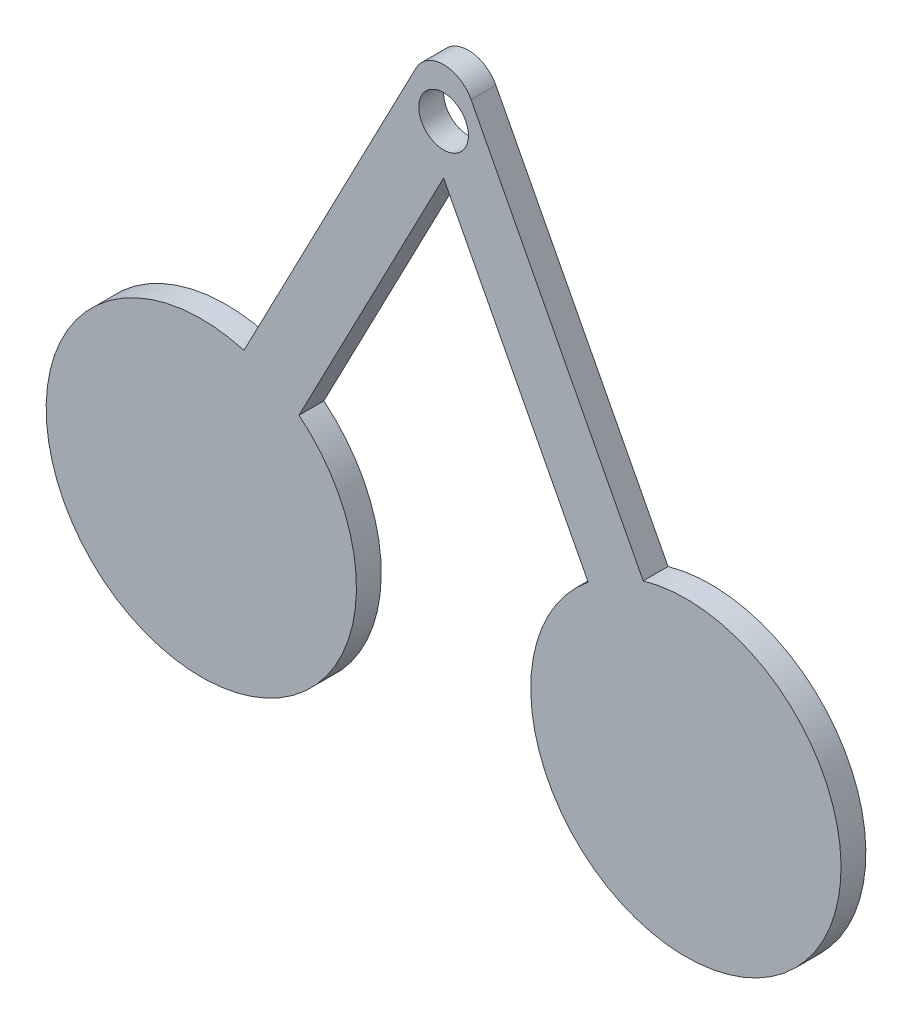
SolidWorks part; units mm, degrees
ref_plane "Front Plane" through (0, 0, 0) normal (0, 0, 1) x (1, 0, 0)
ref_plane "Top Plane" through (0, 0, 0) normal (0, 1, 0) x (1, 0, 0)
ref_plane "Right Plane" through (0, 0, 0) normal (1, 0, 0) x (0, 0, -1)
ref_axis "X" through (-88.99, 0, 0) along (1, 0, 0)
ref_axis "Y" through (0, 55, 0) along (0, -1, 0)
ref_axis "Z" through (0, 0, -88.99) along (0, 0, 1)
sketch "Sketch1" plane through (0, 0, 0) normal (0, 0, 1) x (1, 0, 0)
  line L0 (0, 0) -> (39.0425, 0) construction
  line L1 (-2.1651, 1.25) -> (0, 0) construction
  line L2 (0, 0) -> (19.5213, 37.5) construction
  line L3 (19.5213, 37.5) -> (39.0425, 0) construction
  line L4 (-2.2175, 1.1544) -> (19.5213, 42.9142) construction
  line L5 (19.5213, 32.0858) -> (31.1698, 9.7092)
  line L6 (3.4377, 12.018) -> (17.3037, 38.6544)
  line L7 (21.7388, 38.6544) -> (35.6048, 12.018)
  line L8 (7.8728, 9.7092) -> (19.5213, 32.0858)
  line L9 (2.2175, -1.1544) -> (19.5213, 32.0858) construction
  line L10 (19.5213, 42.9142) -> (41.2601, 1.1544) construction
  line L11 (19.5213, 32.0858) -> (36.825, -1.1544) construction
  arc A0 (3.4377, 12.018) -> (7.8728, 9.7092) centre (0, 0) ccw
  arc A1 (31.1698, 9.7092) -> (35.6048, 12.018) centre (39.0425, 0) ccw
  arc A2 (21.7388, 38.6544) -> (17.3037, 38.6544) centre (19.5213, 37.5) ccw
  dimension "D1" = 25
  dimension "D2" = 25
  dimension "D3" = 55
  dimension "D4" = 37.5
  dimension "D5" = 150
  dimension "D6" = 2.5
  dimension "D7" = 2.5
extrude "Boss-Extrude1" add sketch "Sketch1" along normal blind 2
sketch "Sketch2" plane through (0, 0, 2) normal (0, 0, 1) x (1, 0, 0)
  line L0 (19.5213, 40) -> (19.5213, 32.0858) construction
  circle A0 centre (19.5213, 36.0429) radius 2
  arc A1 (21.7388, 38.6544) -> (17.3037, 38.6544) centre (19.5213, 37.5) ccw construction
  point P6 (19.5213, 42.9142)
  point P7 (19.5213, 40)
extrude "Cut-Extrude1" cut sketch "Sketch2" against normal blind 2
